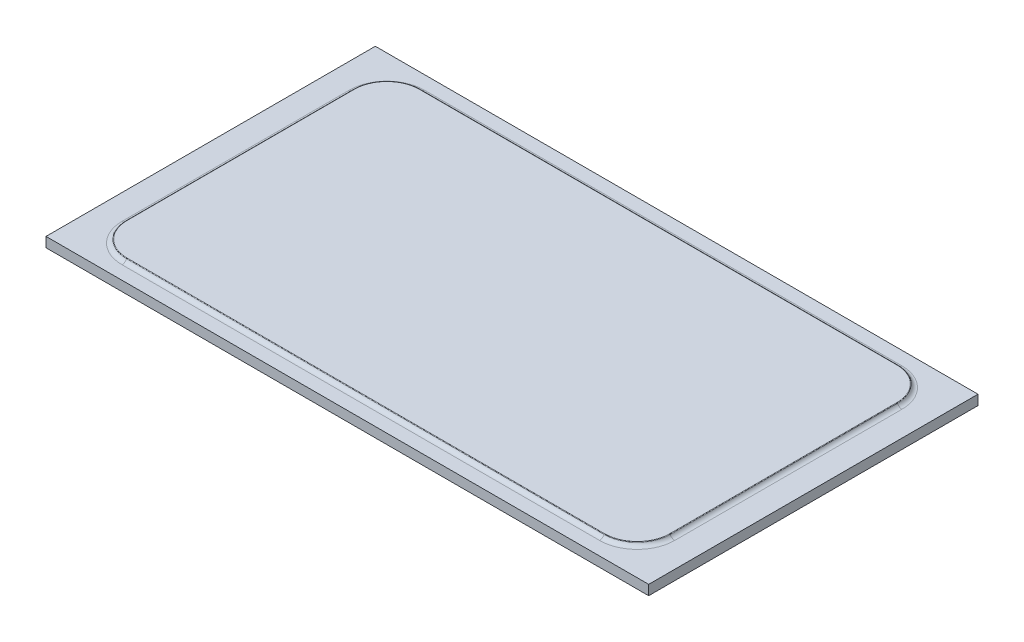
SolidWorks part; units mm, degrees
ref_plane "前视基准面" through (0, 0, 0) normal (0, 0, 1) x (1, 0, 0)
ref_plane "上视基准面" through (0, 0, 0) normal (0, 1, 0) x (1, 0, 0)
ref_plane "右视基准面" through (0, 0, 0) normal (1, 0, 0) x (0, 0, -1)
sketch "草图1" plane through (0, 0, 0) normal (0, 1, 0) x (1, 0, 0)
  line L1 (91.5, 50) -> (-91.5, 50)
  line L2 (91.5, 50) -> (91.5, -50)
  line L3 (91.5, -50) -> (-91.5, -50)
  line L4 (-91.5, 50) -> (-91.5, -50)
  line L5 (91.5, 50) -> (-91.5, -50) construction
  line L6 (91.5, -50) -> (-91.5, 50) construction
  point P0 (0, 0)
  point P6 (0, 0)
  dimension "D1" = 183
  dimension "D2" = 100
extrude "凸台-拉伸1" add sketch "草图1" along normal blind 3
sketch "草图2" plane through (0, 3, 0) normal (0, 1, 0) x (1, 0, 0)
  line L1 (82.5, 44.5) -> (-82.5, 44.5)
  line L2 (82.5, 44.5) -> (82.5, -44.5)
  line L3 (82.5, -44.5) -> (-82.5, -44.5)
  line L4 (-82.5, 44.5) -> (-82.5, -44.5)
  line L5 (82.5, 44.5) -> (-82.5, -44.5) construction
  line L6 (82.5, -44.5) -> (-82.5, 44.5) construction
  point P0 (0, 0)
  dimension "D1" = 165
  dimension "D2" = 89
extrude "凸台-拉伸2" add sketch "草图2" along normal blind 1
fillet "圆角1" radius 10 4 edges at (-82.5, 3.5, -44.5) (82.5, 3.5, -44.5) (82.5, 3.5, 44.5) (-82.5, 3.5, 44.5)
fillet "圆角2" radius 1.5 8 edges at (-79.5711, 3, 41.5711) (-82.5, 3, 0) (-79.5711, 3, -41.5711) (0, 3, -44.5) (79.5711, 3, -41.5711) (82.5, 3, 0) (79.5711, 3, 41.5711) (0, 3, 44.5)
fillet "圆角3" radius 0.2 8 edges at (-79.5711, 4, 41.5711) (-82.5, 4, 0) (-79.5711, 4, -41.5711) (0, 4, -44.5) (79.5711, 4, -41.5711) (82.5, 4, 0) (79.5711, 4, 41.5711) (0, 4, 44.5)
sketch "方向草图" plane through (0, 3, 0) normal (0, 1, 0) x (1, 0, 0)
  line L0 (72.5, -45.9142) -> (-72.5, -45.9142) construction
  line L1 (-83.9142, -34.5) -> (-83.9142, 34.5) construction
  line L2 (-72.5, 45.9142) -> (72.5, 45.9142) construction
  line L3 (83.9142, 34.5) -> (83.9142, -34.5) construction
  line L4 (-91.5, 50) -> (-91.5, -50) construction
  line L5 (-91.5, -50) -> (91.5, -50) construction
  line L6 (91.5, -50) -> (91.5, 50) construction
  line L7 (91.5, 50) -> (-91.5, 50) construction
  line L8 (72.5, -45.9142) -> (-72.5, -45.9142)
  line L9 (-83.9142, -34.5) -> (-83.9142, 34.5)
  line L10 (-72.5, 45.9142) -> (72.5, 45.9142)
  line L11 (83.9142, 34.5) -> (83.9142, -34.5)
  line L12 (-91.5, 50) -> (-91.5, -50) construction
  line L13 (-91.5, -50) -> (91.5, -50) construction
  line L14 (91.5, -50) -> (91.5, 50) construction
  line L15 (91.5, 50) -> (-91.5, 50) construction
  arc A0 (-83.9142, -34.5) -> (-72.5, -45.9142) centre (-72.5, -34.5) ccw construction
  arc A1 (-72.5, 45.9142) -> (-83.9142, 34.5) centre (-72.5, 34.5) ccw construction
  arc A2 (83.9142, 34.5) -> (72.5, 45.9142) centre (72.5, 34.5) ccw construction
  arc A3 (72.5, -45.9142) -> (83.9142, -34.5) centre (72.5, -34.5) ccw construction
  arc A4 (-83.9142, -34.5) -> (-72.5, -45.9142) centre (-72.5, -34.5) ccw
  arc A5 (-72.5, 45.9142) -> (-83.9142, 34.5) centre (-72.5, 34.5) ccw
  arc A6 (83.9142, 34.5) -> (72.5, 45.9142) centre (72.5, 34.5) ccw
  arc A7 (72.5, -45.9142) -> (83.9142, -34.5) centre (72.5, -34.5) ccw
  point P14 (0, 0)
other "成形工具1"
